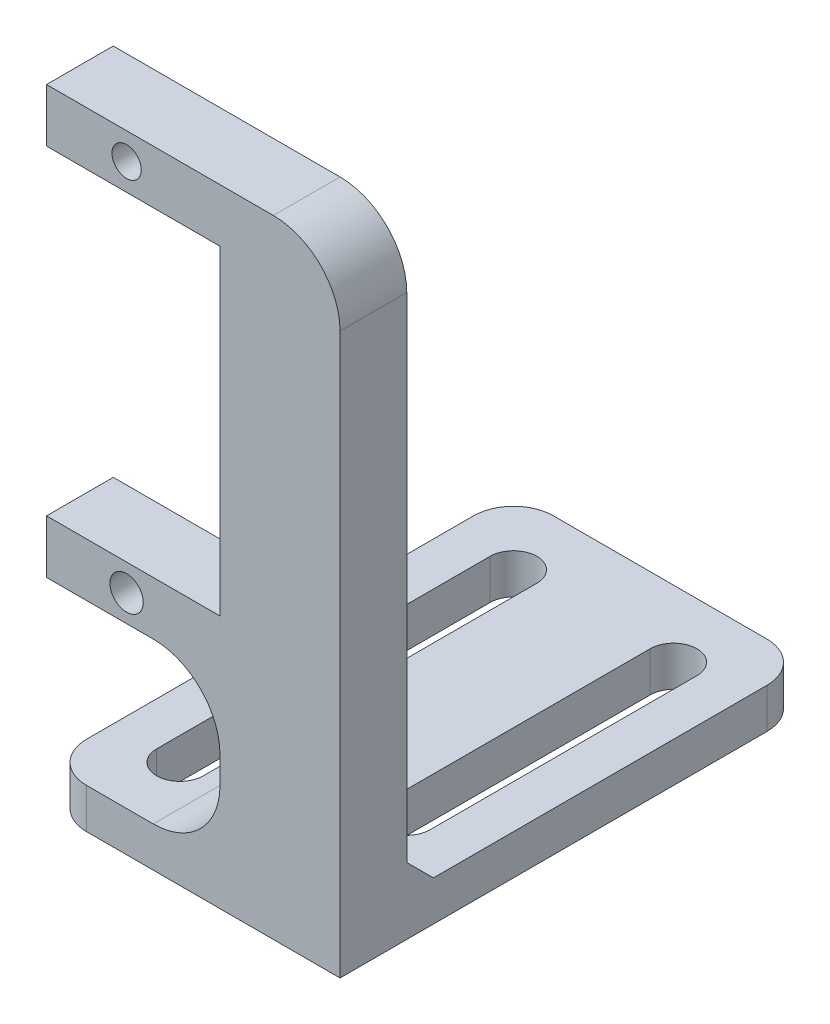
SolidWorks part; units mm, degrees
ref_plane "前视基准面" through (0, 0, 0) normal (0, 0, 1) x (1, 0, 0)
ref_plane "上视基准面" through (0, 0, 0) normal (0, 1, 0) x (1, 0, 0)
ref_plane "右视基准面" through (0, 0, 0) normal (1, 0, 0) x (0, 0, -1)
sketch "草图1" plane through (0, 0, 0) normal (0, 0, 1) x (1, 0, 0)
  line L0 (0, 16) -> (0, -16) construction
  line L1 (-6, 12) -> (6, 12)
  line L2 (-6, 12) -> (-6, -12)
  line L3 (-6, -12) -> (6, -12)
  line L4 (6, 12) -> (6, -12)
  line L5 (-6, 12) -> (6, -12) construction
  line L6 (-6, -12) -> (6, 12) construction
  line L7 (-6, 16) -> (6, 16)
  line L8 (-6, 16) -> (-6, -16)
  line L9 (-6, -16) -> (6, -16)
  line L10 (6, 16) -> (6, -16)
  line L11 (-6, 16) -> (6, -16) construction
  line L12 (-6, -16) -> (6, 16) construction
  line L13 (0, 14) -> (0, -14) construction
  line L14 (6, 12) -> (7, 12)
  line L15 (7, 12) -> (7, -12)
  line L16 (7, -12) -> (6, -12)
  line L17 (6, 16) -> (16, 16)
  line L18 (16, 16) -> (16, -28)
  line L19 (16, -28) -> (16, -31)
  line L20 (16, -31) -> (7, -31)
  line L21 (6, -16) -> (7, -16)
  line L22 (7, -16) -> (7, -31)
  line L24 (16, -28) -> (7, -28)
  line L25 (7, -28) -> (-6, -28)
  line L26 (7, -31) -> (-6, -31)
  line L27 (-6, -31) -> (-6, -28)
  circle A0 centre (0, 14) radius 1.1
  circle A1 centre (0, -14) radius 1.25
  point P0 (0, 0)
  point P6 (0, 0)
  point P14 (0, 0)
  point P20 (0, 0)
  dimension "D5" = 2.2
  dimension "D6" = 2.5
  dimension "D1" = 12
  dimension "D2" = 24
  dimension "D3" = 12
  dimension "D4" = 32
  dimension "D7" = 28
  dimension "D8" = 1
  dimension "D9" = 15
  dimension "D10" = 3
  dimension "D11" = 10
  dimension "D13" = 1
  dimension "D14" = 13
extrude "凸台-拉伸1" add sketch "草图1" along normal mid plane 5 contours L22 L18 L17 L10 L14 L15 L16 L21 | L10 L7 L8 L1 A0 | L10 L3 L8 L9 A1 region at (-5.8735, 14, 0) region at (11.401, -5.8812, 0) region at (0, -12.1265, 0)
extrude "凸台-拉伸3" add sketch "草图1<5>" against normal blind 35 from offset 2.5 contours L24 L22 | L27 L26 L22 L25 region at (11.5, -29.5, 0) region at (0.5, -29.5, 0)
sketch "草图1<5>" plane through (0, 0, 0) normal (0, 0, 1) x (1, 0, 0) same geometry as "草图1"
sketch "草图2" plane through (0, -28, 0) normal (0, 1, 0) x (1, 0, 0)
  line L0 (-2.75, 27.5) -> (-2.75, 2.5)
  line L1 (0.75, 2.5) -> (0.75, 27.5)
  line L2 (9.25, 27.5) -> (9.25, 7.5)
  line L3 (12.75, 7.5) -> (12.75, 27.5)
  line L6 (7, 2.5) -> (16, 2.5)
  line L7 (16, 2.5) -> (16, 32.5)
  line L8 (16, 32.5) -> (-6, 32.5)
  line L9 (-6, 32.5) -> (-6, -2.5)
  line L10 (-6, -2.5) -> (7, -2.5)
  line L11 (7, -2.5) -> (7, 2.5)
  line L12 (7, 2.5) -> (16, 2.5)
  line L13 (16, 2.5) -> (16, 32.5)
  line L14 (16, 32.5) -> (-6, 32.5)
  line L15 (-6, 32.5) -> (-6, -2.5)
  line L16 (-6, -2.5) -> (7, -2.5)
  line L17 (7, -2.5) -> (7, 2.5)
  circle A0 centre (-1, 27.5) radius 1.75
  circle A1 centre (-1, 2.5) radius 1.75
  circle A2 centre (11, 27.5) radius 1.75
  circle A3 centre (11, 7.5) radius 1.75
  point P22 (14.7561, 24.5282)
  point P23 (14.2536, 9.5586)
  point P24 (10.0794, 9.2707)
  point P25 (9.3597, 23.8085)
  point P26 (-1.173, 24.5282)
  point P27 (-2.5872, 23.1368)
  point P28 (2.3547, 9.6545)
  point P29 (-2.0594, 9.4147)
  point P30 (-1, 0.9771)
  dimension "D2" = 3.5
  dimension "D3" = 3.5
  dimension "D4" = 3.5
  dimension "D5" = 3.5
  dimension "D6" = 5
  dimension "D7" = 5
  dimension "D8" = 5
  dimension "D9" = 5
  dimension "D10" = 5
  dimension "D11" = 5
  dimension "D1" = 0
extrude "切除-拉伸1" cut sketch "草图2" against normal blind 20 contours A1 L1 A0 L0 | A0 | A1 | A3 | A3 L3 A2 L2 | A2 region at (-1, -28, -15) region at (-1, -28, -27.5) region at (-1, -28, -2.5) region at (11, -28, -17.5) region at (11, -28, -27.5) region at (11, -28, -7.5)
fillet "圆角1" radius 5 2 edges at (7, -28, 0) (7, -16, 0)
fillet "圆角5" radius 3 3 edges at (16, -29.5, -32.5) (-6, -29.5, 2.5) (-6, -29.5, -32.5)
chamfer "倒角1" distance 2 angle 45 1 edges at (9, -28, -2.5)
fillet "圆角6" radius 5 1 edges at (16, 16, 0)
